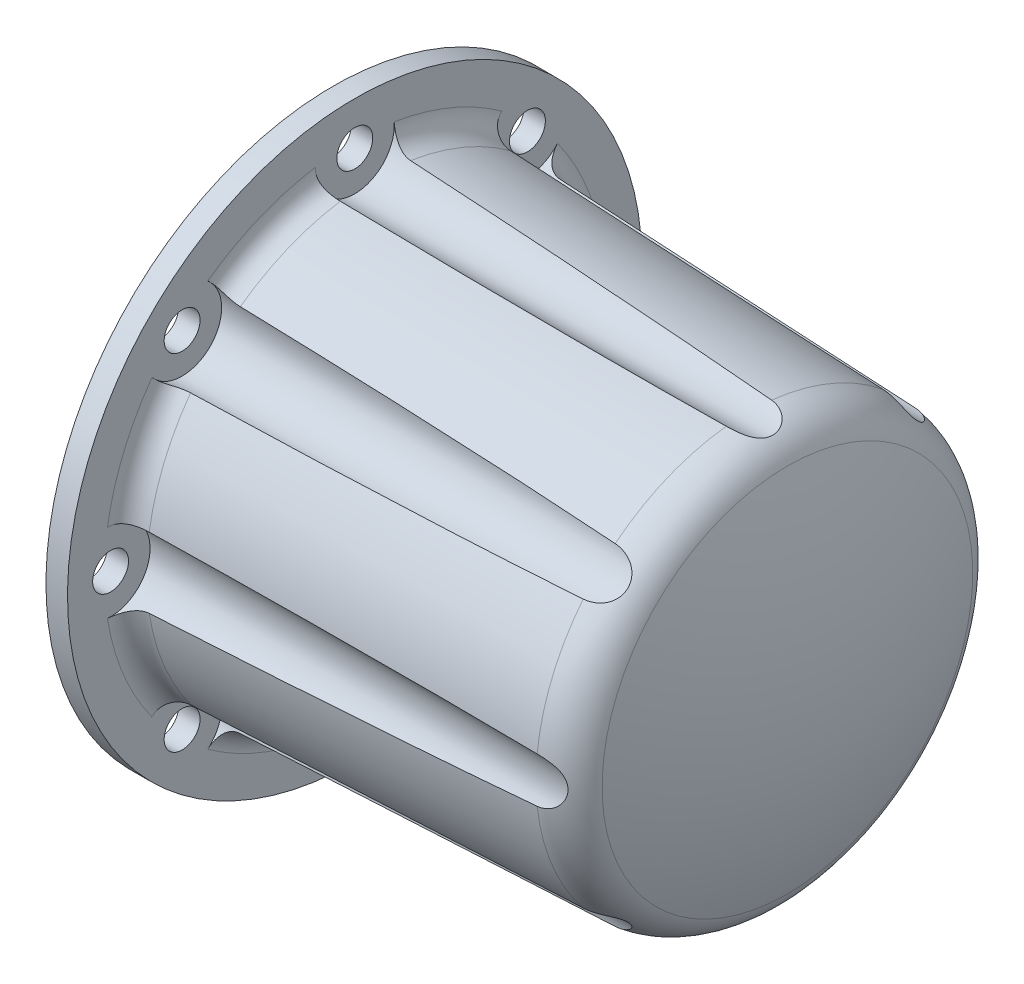
SolidWorks part; units mm, degrees
material "CA"
ref_plane "Płaszczyzna przednia" through (0, 0, 0) normal (0, 0, 1) x (1, 0, 0)
ref_plane "Płaszczyzna górna" through (0, 0, 0) normal (0, 1, 0) x (1, 0, 0)
ref_plane "Płaszczyzna prawa" through (0, 0, 0) normal (1, 0, 0) x (0, 0, -1)
sketch "Szkic1" plane through (0, 0, 0) normal (0, 0, 1) x (1, 0, 0)
  line L0 (-66, 26.5) -> (-10.9941, 26.5)
  line L1 (-65, 32) -> (-10.1082, 29.6628)
  line L2 (-65, 40) -> (-65, 32)
  line L3 (-65, 40) -> (-68, 40)
  line L4 (-68, 40) -> (-68, 28.5)
  line L5 (-68, 28.5) -> (-66, 26.5)
  line L6 (-3, 0) -> (0, 0)
  arc A0 (-7.2385, 23.8767) -> (-10.9941, 26.5) centre (-10.9941, 22.5) ccw
  arc A1 (-3, 0) -> (-7.2385, 23.8767) centre (-72.3723, 0) ccw
  arc A2 (-4.7579, 25.8078) -> (-10.1082, 29.6628) centre (-10.3634, 23.6682) ccw
  arc A3 (0, 0) -> (-4.7579, 25.8078) centre (-72.3723, 0) ccw
revolve "Obrót1" add sketch "Szkic1" angle 360 about L6
fillet "Zaokrąglenie1" radius 3 1 edges at (-65, -32, 0)
sketch "Szkic2" plane through (-65, 0, 0) normal (1, 0, 0) x (0, 0, -1)
  circle A0 centre (0, 34) radius 5.5
  circle A1 centre (24.0416, 24.0416) radius 5.5
  circle A2 centre (34, 0) radius 5.5
  circle A3 centre (24.0416, -24.0416) radius 5.5
  circle A4 centre (0, -34) radius 5.5
  circle A5 centre (-24.0416, -24.0416) radius 5.5
  circle A6 centre (-34, 0) radius 5.5
  circle A7 centre (-24.0416, 24.0416) radius 5.5
  point P20 (0, 0)
  dimension "D2" = 11
  dimension "D1" = 34
  dimension "D3" = 8
extrude "Wytnij-wyciągnięcie1" cut sketch "Szkic2" along normal through all contours A7 | A6 | A5 | A4 | A3 | A2 | A1 | A0
sketch "Szkic3" plane through (-65, 0, 0) normal (1, 0, 0) x (0, 0, -1)
  circle A0 centre (0, 34) radius 2.5
  circle A1 centre (24.0416, 24.0416) radius 2.5
  circle A2 centre (34, 0) radius 2.5
  circle A3 centre (24.0416, -24.0416) radius 2.5
  circle A4 centre (0, -34) radius 2.5
  circle A5 centre (-24.0416, -24.0416) radius 2.5
  circle A6 centre (-34, 0) radius 2.5
  circle A7 centre (-24.0416, 24.0416) radius 2.5
  point P19 (0, 0)
  dimension "D1" = 5
  dimension "D2" = 8
extrude "Wytnij-wyciągnięcie2" cut sketch "Szkic3" against normal through all
